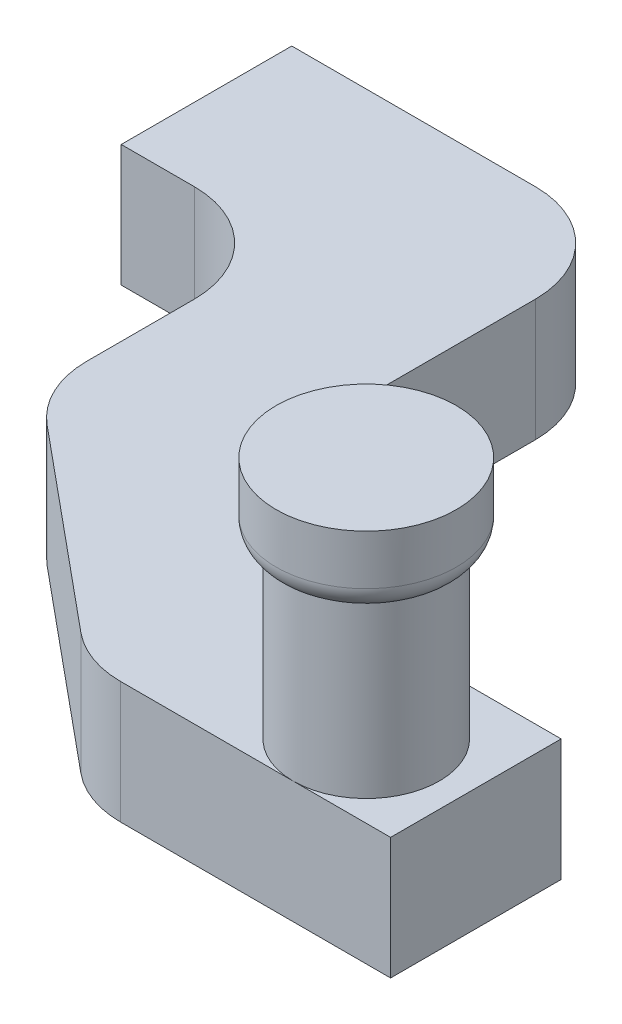
SolidWorks part; units mm, degrees
ref_plane "Front Plane" through (0, 0, 0) normal (0, 0, 1) x (1, 0, 0)
ref_plane "Top Plane" through (0, 0, 0) normal (0, 1, 0) x (1, 0, 0)
ref_plane "Right Plane" through (0, 0, 0) normal (1, 0, 0) x (0, 0, -1)
sketch "Sketch1" plane through (0, 0, 0) normal (0, 1, 0) x (1, 0, 0)
  line L0 (0, 0) -> (7, 0)
  line L1 (7, 0) -> (7, -7)
  line L2 (7, -7) -> (10.0804, -9.5517)
  line L3 (10.0804, -9.5517) -> (15.0804, -9.5517)
  line L4 (0, -3.5) -> (3.5, -3.5)
  line L5 (3.5, -3.5) -> (3.5, -8.6456)
  line L6 (3.5, -8.6456) -> (8.8191, -13.0517)
  line L7 (8.8191, -13.0517) -> (15.0804, -13.0517)
  line L8 (15.0804, -9.5517) -> (15.0804, -13.0517)
  line L9 (0, 0) -> (0, -3.5)
  dimension "D1" = 7
  dimension "D2" = 7
  dimension "D3" = 4
  dimension "D4" = 5
  dimension "D5" = 3.5
extrude "Boss-Extrude1" add sketch "Sketch1" along normal blind 2.5
fillet "Fillet1" radius 2 5 edges at (7, 1.25, 7) (3.5, 1.25, 8.6456) (3.5, 1.25, 3.5) (7, 1.25, 0) (8.8191, 1.25, 13.0517)
sketch "Sketch2" plane through (0, 2.5, 0) normal (0, 1, 0) x (1, 0, 0)
  line L0 (15.0804, -9.5517) -> (10.0804, -9.5517) construction
  line L1 (15.0804, -13.0517) -> (15.0804, -9.5517) construction
  circle A0 centre (13.0804, -11.5517) radius 1.5
  dimension "D1" = 2
  dimension "D2" = 2
extrude "Boss-Extrude2" add sketch "Sketch2" along normal blind 3.5
sketch "Sketch3" plane through (0, 6, 0) normal (0, 1, 0) x (1, 0, 0)
  circle A0 centre (13.0804, -11.5517) radius 1.85
extrude "Boss-Extrude3" add sketch "Sketch3" along normal blind 1.5
fillet "Fillet2" radius 0.5 1 edges at (13.0804, 6, 13.4017)
sketch "Sketch4" plane through (0, 0, 0) normal (0, -1, 0) x (-1, 0, 0)
  circle A0 centre (-1.5563, -1.4668) radius 1.5
extrude "Boss-Extrude4" add sketch "Sketch4" along normal blind 3
sketch "Sketch5" plane through (0, -3, 0) normal (0, -1, 0) x (1, 0, 0)
  circle A0 centre (1.5536, 1.4529) radius 1.72
extrude "Boss-Extrude5" add sketch "Sketch5" along normal blind 1
fillet "Fillet3" radius 0.5 1 edges at (1.5536, -3, -0.2671)
